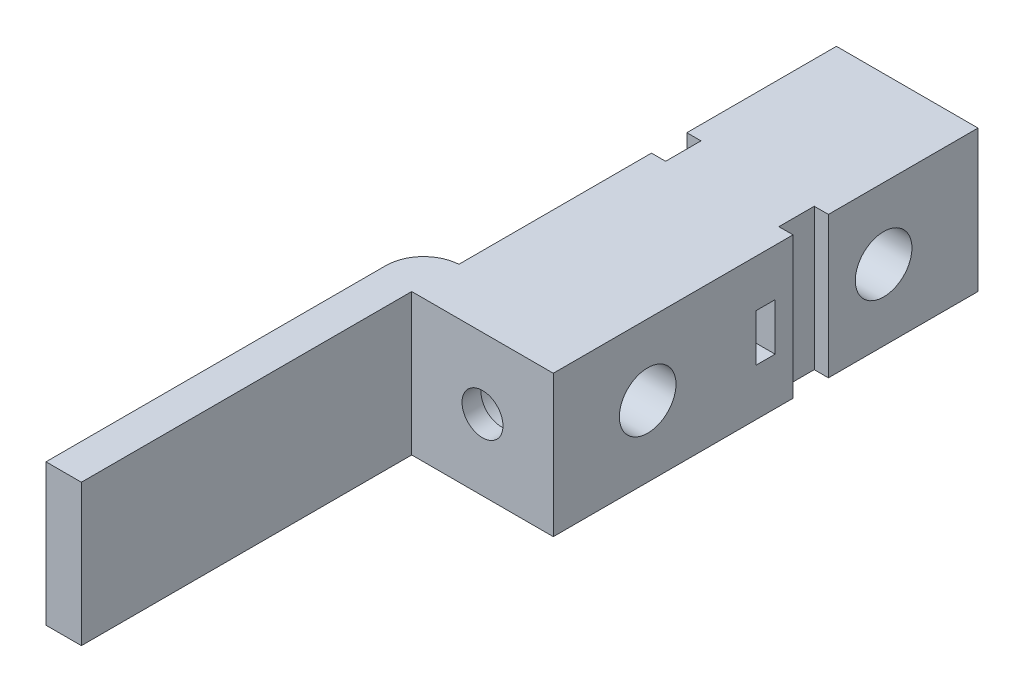
SolidWorks part; units mm, degrees
ref_plane "Front Plane" through (0, 0, 0) normal (0, 0, 1) x (1, 0, 0)
ref_plane "Top Plane" through (0, 0, 0) normal (0, 1, 0) x (1, 0, 0)
ref_plane "Right Plane" through (0, 0, 0) normal (1, 0, 0) x (0, 0, -1)
sketch "Sketch1" plane through (0, 0, 0) normal (0, 0, 1) x (1, 0, 0)
  line L1 (9.525, -9.525) -> (-9.525, -9.525)
  line L2 (9.525, -9.525) -> (9.525, 9.525)
  line L3 (9.525, 9.525) -> (-9.525, 9.525)
  line L4 (-9.525, -9.525) -> (-9.525, 9.525)
  line L5 (9.525, -9.525) -> (-9.525, 9.525) construction
  line L6 (9.525, 9.525) -> (-9.525, -9.525) construction
  point P0 (0, 0)
  dimension "D1" = 19.05
  dimension "D2" = 19.05
extrude "Boss-Extrude1" add sketch "Sketch1" along normal blind 57.15
sketch "Sketch2" plane through (0, 0, 0) normal (0, 0, -1) x (-1, 0, 0)
  circle A0 centre (0, 0) radius 2.7559
  dimension "D1" = 5.5118
extrude "Cut-Extrude1" cut sketch "Sketch2" against normal blind 57.15 contours A0
sketch "Sketch3" plane through (0, 0, 0) normal (0, 0, -1) x (-1, 0, 0)
  circle A0 centre (0, 0) radius 4.445
  dimension "D1" = 8.89
extrude "Cut-Extrude2" cut sketch "Sketch3" against normal blind 54.61
sketch "Sketch4" plane through (9.525, 0, 0) normal (1, 0, 0) x (0, 0, -1)
  line L0 (-44.45, 0) -> (-57.15, 0)
  line L1 (-57.15, -9.525) -> (-57.15, 9.525) construction
  line L2 (-12.7, 0) -> (0, 0)
  line L3 (0, -9.525) -> (0, 9.525) construction
  circle A0 centre (-44.45, 0) radius 3.81
  circle A1 centre (-12.7, 0) radius 3.81
  dimension "D1" = 7.62
  dimension "D3" = 7.62
  dimension "D2" = 12.7
  dimension "D4" = 12.7
extrude "Cut-Extrude3" cut sketch "Sketch4" against normal blind 54.61 contours A1 | A0 region at (9.525, 0, 16.4022)
sketch "Sketch6" plane through (9.525, 0, 0) normal (1, 0, 0) x (0, 0, -1)
  line L0 (0, 0) -> (-57.15, 0) construction
  line L1 (-27.305, -3.175) -> (-29.845, -3.175)
  line L2 (-27.305, -3.175) -> (-27.305, 3.175)
  line L3 (-27.305, 3.175) -> (-29.845, 3.175)
  line L4 (-29.845, -3.175) -> (-29.845, 3.175)
  line L5 (-27.305, -3.175) -> (-29.845, 3.175) construction
  line L6 (-27.305, 3.175) -> (-29.845, -3.175) construction
  line L7 (-57.15, -9.525) -> (-57.15, 9.525) construction
  point P0 (-28.575, 0)
  point P10 (0, 0)
  dimension "D1" = 6.35
  dimension "D2" = 2.54
extrude "Cut-Extrude4" cut sketch "Sketch6" against normal blind 54.61 contours L2 L1 L4 L3
sketch "Sketch7" plane through (0, -9.525, 0) normal (0, -1, 0) x (1, 0, 0)
  line L0 (-9.525, 0) -> (-9.525, 24.892) construction
  line L1 (-9.525, 57.15) -> (-9.525, 0) construction
  line L2 (-9.525, 24.892) -> (9.525, 24.892) construction
  line L3 (9.525, 57.15) -> (9.525, 0) construction
  line L4 (-9.525, 24.892) -> (-7.62, 24.892)
  line L5 (-9.525, 24.892) -> (-9.525, 20.1295)
  line L6 (-9.525, 20.1295) -> (-7.62, 20.1295)
  line L7 (-7.62, 24.892) -> (-7.62, 20.1295)
  line L9 (9.525, 24.892) -> (7.62, 24.892)
  line L10 (9.525, 24.892) -> (9.525, 20.1295)
  line L11 (9.525, 20.1295) -> (7.62, 20.1295)
  line L12 (7.62, 24.892) -> (7.62, 20.1295)
  dimension "D1" = 24.892
  dimension "D2" = 1.905
  dimension "D3" = 4.7625
  dimension "D4" = 1.905
  dimension "D5" = 4.7625
extrude "Cut-Extrude5" cut sketch "Sketch7" against normal blind 54.61
sketch "Sketch8" plane through (-9.525, 0, 0) normal (-1, 0, 0) x (0, 0, 1)
  line L0 (57.15, -9.525) -> (24.892, -9.525) construction
  line L1 (57.15, 9.525) -> (50.8, 9.525)
  line L2 (57.15, 9.525) -> (57.15, -9.525)
  line L3 (57.15, -9.525) -> (50.8, -9.525)
  line L4 (50.8, 9.525) -> (50.8, -9.525)
  line L6 (57.15, 9.525) -> (101.6, 9.525)
  line L7 (57.15, 9.525) -> (57.15, -9.525)
  line L8 (57.15, -9.525) -> (101.6, -9.525)
  line L9 (101.6, 9.525) -> (101.6, -9.525)
  dimension "D1" = 6.35
  dimension "D2" = 44.45
extrude "Boss-Extrude2" add sketch "Sketch8" along normal blind 4.7625 contours L2 L1 L4 L3 | L7 L6 L9 L8
fillet "Fillet2" radius 5.08 1 edges at (-14.2875, 0, 50.8)
